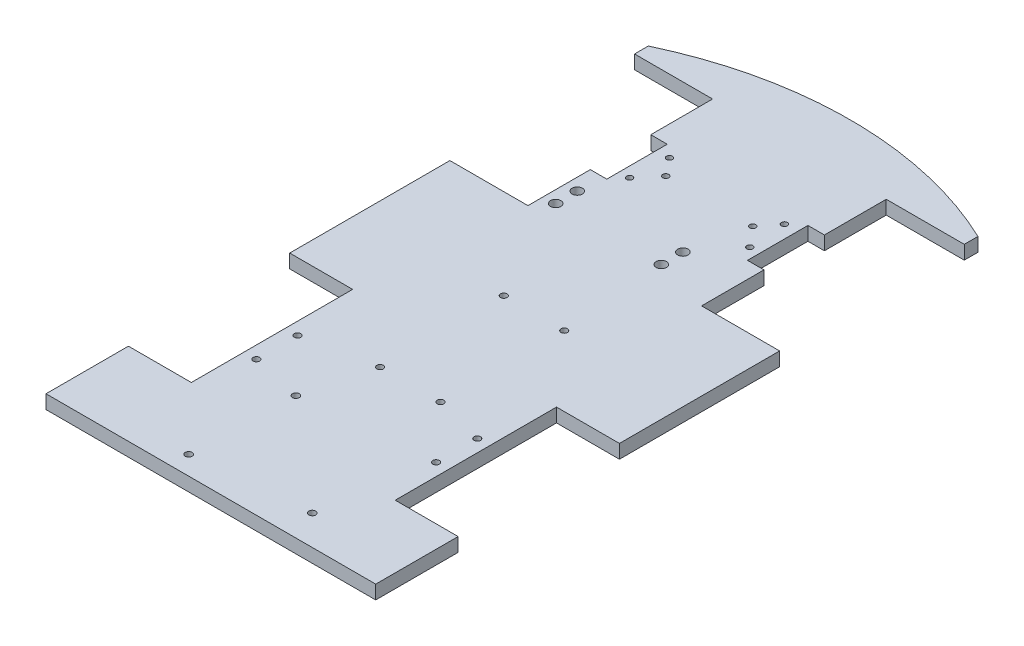
SolidWorks part; units mm, degrees
material "Oak"
ref_plane "Front Plane" through (0, 0, 0) normal (0, 0, 1) x (1, 0, 0)
ref_plane "Top Plane" through (0, 0, 0) normal (0, 1, 0) x (1, 0, 0)
ref_plane "Right Plane" through (0, 0, 0) normal (1, 0, 0) x (0, 0, -1)
sketch "Sketch1" plane through (0, 0, 0) normal (0, 1, 0) x (1, 0, 0)
  line L0 (50.292, 32.512) -> (76.2, 32.512) construction
  line L1 (0, 0) -> (0, -280.955) construction
  line L2 (0, 66.1738) -> (0, -229.362)
  line L3 (76.2, -229.362) -> (0, -229.362)
  line L7 (50.292, 32.512) -> (50.292, -32.512) construction
  line L8 (50.292, -32.512) -> (76.2, -32.512) construction
  line L9 (76.2, 32.512) -> (76.2, -32.512) construction
  line L10 (50.292, 32.512) -> (76.2, -32.512) construction
  line L11 (50.292, -32.512) -> (76.2, 32.512) construction
  line L18 (50.292, -119.888) -> (76.2, -119.888) construction
  line L19 (50.292, -119.888) -> (50.292, -184.912) construction
  line L20 (50.292, -184.912) -> (76.2, -184.912) construction
  line L21 (76.2, -119.888) -> (76.2, -184.912) construction
  line L22 (50.292, -119.888) -> (76.2, -184.912) construction
  line L23 (50.292, -184.912) -> (76.2, -119.888) construction
  line L25 (-76.2, 0) -> (76.2, 0) construction
  line L27 (-76.2, -152.4) -> (76.2, -152.4) construction
  line L28 (76.2, 0) -> (76.2, -152.4) construction
  line L33 (40.132, -42.672) -> (76.2, -42.672)
  line L34 (40.132, 42.672) -> (40.132, 14.097)
  line L35 (40.132, 42.672) -> (76.2, 42.672)
  line L36 (47.117, -191.262) -> (76.2, -191.262)
  line L37 (47.117, -116.713) -> (47.117, -191.262)
  line L38 (47.117, -116.713) -> (76.2, -116.713)
  line L43 (76.2, -42.672) -> (76.2, -116.713)
  line L45 (76.2, 42.672) -> (76.2, 49.022)
  line L47 (76.2, -191.262) -> (76.2, -229.362)
  line L55 (32.512, -13.843) -> (40.132, -13.843)
  line L56 (32.512, 14.097) -> (32.512, -13.843)
  line L57 (32.512, 14.097) -> (40.132, 14.097)
  line L58 (40.132, -13.843) -> (40.132, -42.672)
  arc A0 (0, 66.1738) -> (76.2, 49.022) centre (0, -111.6688) cw
  point P9 (63.246, 0)
  point P19 (63.246, -152.4)
  dimension "D7" = 3.175
  dimension "D8" = 6.35
  dimension "D12" = 7.62
  dimension "D16" = 6.35
  dimension "D1" = 152.4
  dimension "D2" = 152.4
  dimension "D3" = 126.492
  dimension "D4" = 25.908
  dimension "D6" = 3.175
  dimension "D9" = 10.16
  dimension "D10" = 10.16
  dimension "D5" = 65.024
  dimension "D11" = 10.16
  dimension "D13" = 27.94
  dimension "D14" = 28.575
  dimension "D15" = 38.1
extrude "Chassis" add sketch "Sketch1" along normal blind 6.35 contours L47 L36 L37 L38 L43 L33 L34 L55 L56 L57 L35 L45 region at (30.845, 0, 91.965)
mirror "Mirror1" about plane through (0, 6.35, 0) normal (1, 0, 0) of "Chassis"
sketch "Sketch2" plane through (0, 0, 0) normal (0, 1, 0) x (1, 0, 0)
  circle A0 centre (-26.5557, 9.17) radius 1.3716 construction
  circle A1 centre (-17.7031, -172.3599) radius 1.5875
  circle A2 centre (-17.7031, -172.3599) radius 1.5875
  circle A3 centre (-18.9731, -220.6199) radius 1.5875
  circle A4 centre (-18.9731, -220.6199) radius 1.5875
  circle A5 centre (33.0969, -215.5399) radius 1.5875
  circle A6 centre (33.0969, -215.5399) radius 1.5875
  circle A7 centre (-20.1056, 0.9994) radius 1.3716 construction
  circle A8 centre (-27.7865, -8.0406) radius 1.3716 construction
  circle A9 centre (26.5557, 9.17) radius 1.3716 construction
  circle A10 centre (20.1056, 0.9994) radius 1.3716 construction
  circle A11 centre (27.7865, -8.0406) radius 1.3716 construction
  circle A12 centre (14.2672, -25.46) radius 2.3813 construction
  circle A13 centre (14.2672, -35.4295) radius 2.3813 construction
  circle A14 centre (-34.5516, -25.46) radius 2.3813 construction
  circle A15 centre (-34.5516, -35.4295) radius 2.3813 construction
  circle A16 centre (18.288, -84.328) radius 1.5 construction
  circle A17 centre (-9.652, -84.328) radius 1.5 construction
  circle A18 centre (18.288, -141.478) radius 1.5 construction
  circle A19 centre (-9.652, -141.478) radius 1.5 construction
  circle A20 centre (-41.402, -147.875) radius 1.5 construction
  circle A21 centre (-41.402, -166.925) radius 1.5 construction
  circle A22 centre (41.402, -147.6053) radius 1.5 construction
  circle A23 centre (41.402, -166.6553) radius 1.5 construction
  circle A24 centre (-26.5557, 9.17) radius 1.3716
  circle A25 centre (-20.1056, 0.9994) radius 1.3716
  circle A26 centre (-27.7865, -8.0406) radius 1.3716
  circle A27 centre (26.5557, 9.17) radius 1.3716
  circle A28 centre (20.1056, 0.9994) radius 1.3716
  circle A29 centre (27.7865, -8.0406) radius 1.3716
  circle A30 centre (14.2672, -25.46) radius 2.3812
  circle A31 centre (14.2672, -35.4295) radius 2.3813
  circle A32 centre (-34.5516, -25.46) radius 2.3813
  circle A33 centre (-34.5516, -35.4295) radius 2.3812
  circle A34 centre (18.288, -84.328) radius 1.5
  circle A35 centre (-9.652, -84.328) radius 1.5
  circle A36 centre (18.288, -141.478) radius 1.5
  circle A37 centre (-9.652, -141.478) radius 1.5
  circle A38 centre (-41.402, -147.875) radius 1.5
  circle A39 centre (-41.402, -166.925) radius 1.5
  circle A40 centre (41.402, -147.6053) radius 1.5
  circle A41 centre (41.402, -166.6553) radius 1.5
  dimension "D1" = 0
  dimension "D2" = 0
  dimension "D3" = 0
extrude "Cut-Extrude1" cut sketch "Sketch2" along normal blind 17.78
